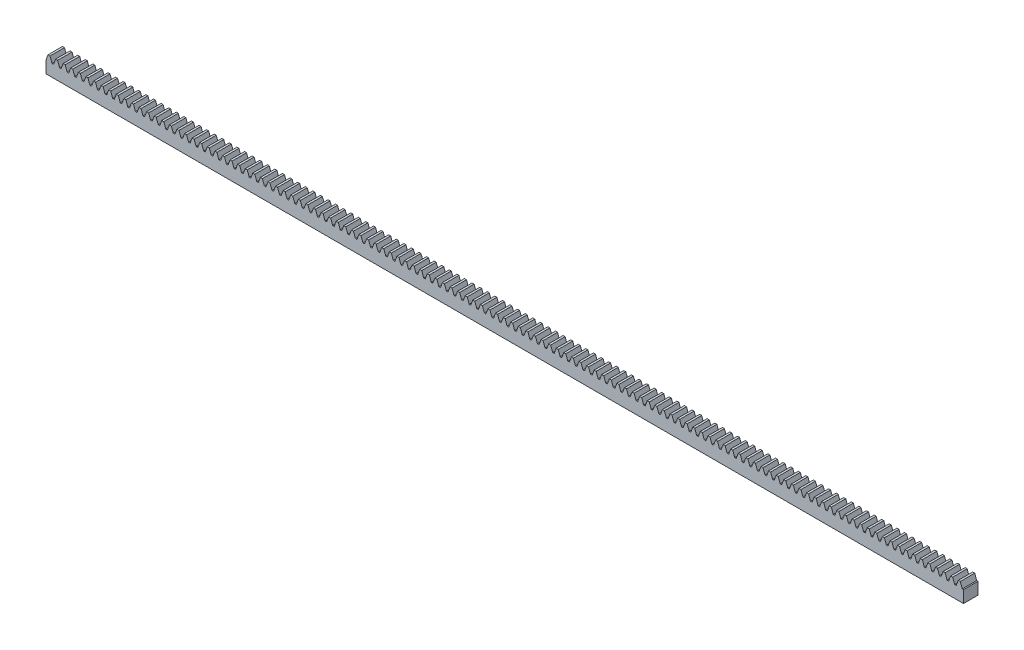
SolidWorks part; units mm, degrees
ref_plane "前视基准面" through (0, 0, 0) normal (0, 0, 1) x (1, 0, 0)
ref_plane "上视基准面" through (0, 0, 0) normal (0, 1, 0) x (1, 0, 0)
ref_plane "右视基准面" through (0, 0, 0) normal (1, 0, 0) x (0, 0, -1)
sketch "草图1" plane through (0, 0, 0) normal (0, 0, 1) x (1, 0, 0)
  line L1 (0, 0) -> (760, 0)
  line L2 (0, 0) -> (0, -10)
  line L3 (0, -10) -> (760, -10)
  line L4 (760, 0) -> (760, -10)
  dimension "D1" = 10
  dimension "L" = 760
extrude "拉伸1" add sketch "草图1" along normal blind 12
sketch "草图2" plane through (0, 0, 12) normal (0, 0, 1) x (1, 0, 0)
  line L0 (0, 0) -> (1.6379, 4.5)
  line L1 (1.6379, 4.5) -> (3.3236, 4.5)
  line L2 (3.3236, 4.5) -> (4.9614, 0)
  line L3 (760, 0) -> (0, 0) construction
  line L4 (0, 0) -> (4.9614, 0)
  line L5 (0.9099, 2.5) -> (4.0515, 2.5) construction
  dimension "D2" = 70
  dimension "alpha" = 110
  dimension "ha" = 2
  dimension "hf" = 2.5
  dimension "S" = 3.1416
extrude "拉伸2" add sketch "草图2" against normal up to surface (12 mm away) up to face at (380, -5, 0)
pattern_linear "阵列(线性)1" count 121 spacing 6.2832 along (1, 0, 0) of "拉伸2"
sketch "草图3" plane through (0, 0, 0) normal (0, 0, -1) x (-1, 0, 0)
  line L0 (-380, -10) -> (-380, 64.2865) construction
  line L1 (0, -10) -> (-760, -10) construction
  line L2 (-179.9519, -4) -> (-580.0481, -4) construction
  line L3 (-564.5296, -4) -> (62.3039, -4)
  line L4 (-380, 51.1157) -> (-380, -143.0253)
  point P10 (-380, -4)
  dimension "D1" = 6
hole_wizard "M6 螺纹孔3" positions "草图20" profile "草图22" tap size "M6" standard "GB"
sketch "草图20" plane through (0, -10, 0) normal (0, -1, 0) x (-1, 0, 0)
  point P0 (-276.4602, -6.2222)
sketch "草图22" plane through (276.4602, -10, 6.2222) normal (1, 0, 0) x (0, 0, -1)
  line L0 (0, 0) -> (0, 8.5022)
  line L1 (0, 8.5022) -> (2.5, 7)
  line L2 (2.5, 7) -> (2.5, 0)
  line L5 (2.5, 0) -> (0, 0)
  line L10 (0, 8.5022) -> (-2.5, 7) construction
  line L11 (0, -6.35) -> (0, 107.95) construction
  dimension "螺纹孔钻头直径" = 5
  dimension "螺纹孔钻头深度" = 7
  dimension "导头角度" = 118
cosmetic thread "孔螺蚊线6" parameters "D1"=7, "D2"=6
pattern_linear "阵列(线性)4" count 6 spacing 50 along (-1, 0, 0) of "M6 螺纹孔3"
pattern_linear "阵列(线性)5" count 10 spacing 50 along (1, 0, 0) of "阵列(线性)4"
equation "\"D2@草图2\" = 180 - \"alpha@草图2\""
equation "\"d\"=\"S@草图2\" * 2"
equation "\"z\"= int(  \"L@草图1\" / (  \"S@草图2\" * 2 ) + 0.5 )"
